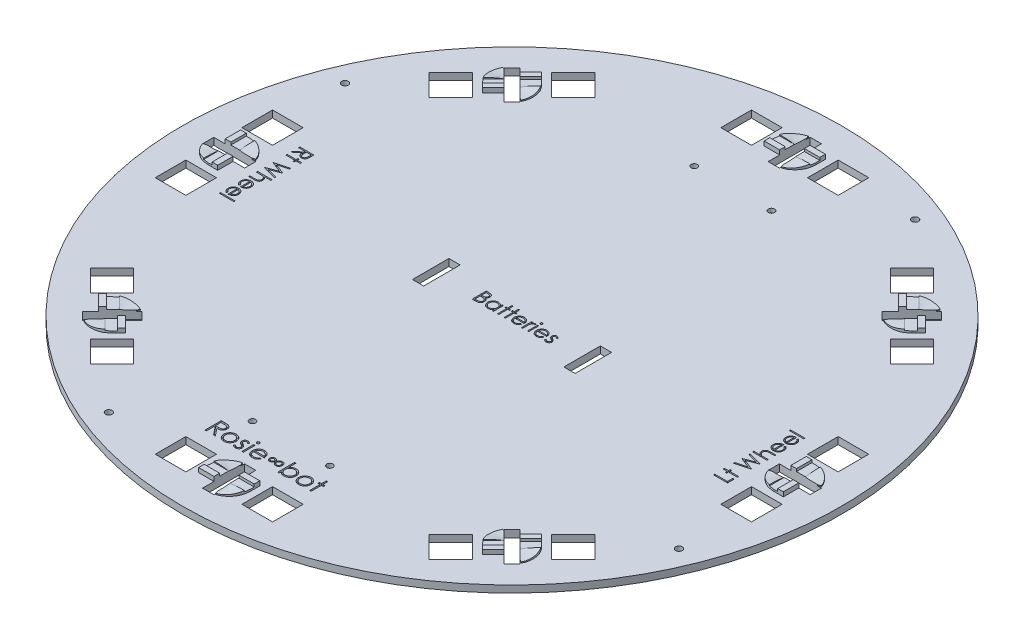
SolidWorks part; units mm, degrees
other "DetailItem1"
ref_plane "Front" through (0, 0, 0) normal (0, 0, 1) x (1, 0, 0)
ref_plane "Top" through (0, 0, 0) normal (0, 1, 0) x (1, 0, 0)
ref_plane "Right" through (0, 0, 0) normal (1, 0, 0) x (0, 0, -1)
sketch "Sketch1" plane through (0, 0, 0) normal (0, 1, 0) x (1, 0, 0)
  circle A0 centre (0, 0) radius 149.225
  dimension "D1" = 298.45
extrude "Boss-Extrude1" add sketch "Sketch1" along normal blind 3.175 contours A0
sketch "Sketch2" plane through (0, 3.175, 0) normal (0, 1, 0) x (1, 0, 0)
  line L1 (-2.54, -137.5833) -> (2.54, -137.5833)
  line L2 (-2.54, -137.5833) -> (-2.54, -118.5333)
  line L3 (-2.54, -118.5333) -> (2.54, -118.5333)
  line L4 (2.54, -137.5833) -> (2.54, -118.5333)
  circle A0 centre (0, 0) radius 149.225 construction
  point P4 (0, -118.5333)
  dimension "D1" = 5.08
  dimension "D2" = 19.05
  dimension "D3" = 137.5833
extrude "Cut-Extrude1" cut sketch "Sketch2" against normal up to next and the other way through all contours L1 L4 L3 L2
sketch "Sketch4" plane through (0, 3.175, 0) normal (0, 1, 0) x (1, 0, 0)
  line L0 (0, -128.0583) -> (-2.9434, -118.9995) construction
  line L1 (-2.9434, -118.9995) -> (0, -128.0583) construction
  line L2 (0, -128.0583) -> (-5.5987, -120.3525) construction
  line L3 (0, -128.0583) -> (-7.7059, -122.4597) construction
  line L4 (0, -128.0583) -> (-9.0588, -125.115) construction
  line L5 (0, -128.0583) -> (-9.525, -128.0583) construction
  line L9 (2.54, -118.5333) -> (-2.54, -118.5333) construction
  line L10 (2.54, -118.5333) -> (2.54, -137.5833) construction
  line L11 (-2.54, -118.5333) -> (-2.54, -137.5833) construction
  line L12 (2.54, -137.5833) -> (-2.54, -137.5833) construction
  circle A0 centre (0, -128.0583) radius 9.525 construction
  point P16 (0, -118.5333)
  point P19 (2.54, -128.0583)
  dimension "D1" = 18
  dimension "D2" = 18
  dimension "D3" = 18
  dimension "D4" = 18
  dimension "D5" = 18
ref_plane "Plane1" through (-37.6354, 0, 12.2285) normal (0.9511, 0, -0.309) x (-0.309, 0, -0.9511)
ref_plane "Plane2" through (-60.8954, 0, 44.2431) normal (0.809, 0, -0.5878) x (-0.5878, 0, -0.809)
ref_plane "Plane3" through (-60.8954, 0, 83.8153) normal (0.5878, 0, -0.809) x (-0.809, 0, -0.5878)
ref_plane "Plane4" through (-37.6354, 0, 115.8299) normal (0.309, 0, -0.9511) x (-0.9511, 0, -0.309)
ref_plane "Plane5" through (0, 0, 128.0583) normal (0, 0, -1) x (-1, 0, 0)
sketch "Sketch5" plane through (-37.6354, 0, 12.2285) normal (0.9511, 0, -0.309) x (-0.309, 0, -0.9511)
  line L0 (-111.947, 3.175) -> (-130.0646, 3.175) construction
  line L1 (-113.5711, 3.175) -> (-112.2657, 3.175)
  line L2 (-113.5711, 3.175) -> (-113.5711, 3.683)
  line L3 (-113.5711, 3.683) -> (-112.2657, 3.683)
  line L4 (-112.2657, 3.175) -> (-112.2657, 3.683)
  dimension "D2" = 0.508
sketch "Sketch6" plane through (-60.8954, 0, 44.2431) normal (0.809, 0, -0.5878) x (-0.5878, 0, -0.809)
  line L0 (-94.4025, 3.175) -> (-109.8143, 3.175) construction
  line L1 (-99.2801, 3.175) -> (-94.0764, 3.175)
  line L2 (-99.2801, 3.175) -> (-99.2801, 3.775)
  line L3 (-99.2801, 3.775) -> (-94.0764, 3.775)
  line L4 (-94.0764, 3.175) -> (-94.0764, 3.775)
  dimension "D2" = 0.6
sketch "Sketch7" plane through (-60.8954, 0, 83.8153) normal (0.5878, 0, -0.809) x (-0.809, 0, -0.5878)
  line L0 (-67.6172, 3.175) -> (-78.8146, 3.175) construction
  line L1 (-72.1312, 3.175) -> (-65.7458, 3.175)
  line L2 (-72.1312, 3.175) -> (-72.1312, 4.075)
  line L3 (-72.1312, 4.075) -> (-65.7458, 4.075)
  line L4 (-65.7458, 3.175) -> (-65.7458, 4.075)
  dimension "D2" = 0.9
sketch "Sketch10" plane through (-37.6354, 0, 115.8299) normal (0.309, 0, -0.9511) x (-0.9511, 0, -0.309)
  line L0 (-39.5722, 3.175) -> (-30.5134, 3.175) construction
  line L1 (-36.9015, 3.175) -> (-30.0472, 3.175)
  line L2 (-36.9015, 3.175) -> (-36.9015, 4.475)
  line L3 (-36.9015, 4.475) -> (-30.0472, 4.475)
  line L4 (-30.0472, 3.175) -> (-30.0472, 4.475)
  dimension "D3" = 1.3
sketch "Sketch11" plane through (0, 0, 128.0583) normal (0, 0, -1) x (-1, 0, 0)
  line L0 (0, 3.175) -> (9.525, 3.175) construction
  line L1 (2.54, 3.175) -> (9.525, 3.175)
  line L2 (2.54, 3.175) -> (2.54, 4.575)
  line L3 (2.54, 4.575) -> (9.525, 4.575)
  line L4 (9.525, 3.175) -> (9.525, 4.575)
  dimension "D3" = 1.4
loft "Loft1" add profiles "Sketch5", "Sketch6", "Sketch7", "Sketch10", "Sketch11" connector at (-2.54, 3.683, 120.241) connector at (-2.54, 3.775, 124.5623) connector at (-2.54, 4.075, 126.2129) connector at (-2.54, 4.475, 127.233) connector at (-2.54, 4.575, 128.0583)
sketch "Sketch13" plane through (-104.9799, 0, 128.0583) normal (0, 0, -1) x (-1, 0, 0)
  line L6 (-95.4549, 3.175) -> (-102.4399, 3.175)
  line L7 (-95.4549, 3.175) -> (-95.4549, 4.575)
  line L8 (-95.4549, 4.575) -> (-102.4399, 4.575)
  line L9 (-102.4399, 3.175) -> (-102.4399, 4.575)
extrude "Boss-Extrude4" add sketch "Sketch13" against normal blind 1.7907
sketch "Sketch25" plane through (0, 0, 129.849) normal (0, 0, 1) x (1, 0, 0)
  line L0 (-9.525, 4.575) -> (-2.54, 4.575) construction
  line L1 (-9.525, 3.175) -> (-2.54, 3.175)
  line L2 (-9.525, 3.175) -> (-9.525, 5.175)
  line L3 (-9.525, 5.175) -> (-2.54, 5.175)
  line L4 (-2.54, 3.175) -> (-2.54, 5.175)
  dimension "D1" = 0.6
extrude "Boss-Extrude5" add sketch "Sketch25" along normal blind 2.54
sketch "Sketch29" plane through (-2.54, 0, 0) normal (1, 0, 0) x (0, 0, -1)
  line L1 (-129.849, 5.175) -> (-125.749, 5.175)
  line L2 (-129.849, 5.175) -> (-129.849, 4)
  line L3 (-129.849, 4) -> (-125.749, 4)
  line L4 (-125.749, 5.175) -> (-125.749, 4)
  line L5 (-118.5333, 0) -> (-137.5833, 0) construction
  dimension "D1" = 4.1
  dimension "D2" = 4
extrude "Cut-Extrude10" cut sketch "Sketch29" against normal up to next
sketch "Sketch14" plane through (-2.54, 0, 0) normal (1, 0, 0) x (0, 0, -1)
  line L0 (-128.0583, 3.175) -> (-128.0583, 0) construction
  line L1 (-118.5333, 0) -> (-137.5833, 0) construction
ref_plane "Plane6" through (0, 0, 0) normal (1, 0, 0) x (0, 0, -1)
sketch "Sketch15" plane through (0, 0, 0) normal (1, 0, 0) x (0, 0, -1)
  line L0 (-128.0583, 0) -> (-128.0583, 3.175) construction
pattern_circular "CirPattern1" count 2 over 360 about axis through (0, 0, 128.0583) along (0, 1, 0) of "Loft1", "Boss-Extrude5", "Boss-Extrude4", "Cut-Extrude10" reverse direction yes
ref_axis "Axis1" through (0, 50, 0) along (0, -1, 0)
pattern_circular "CirPattern5" count 8 over 360 about axis through (0, 50, 0) along (0, -1, 0) of "CirPattern1", "Cut-Extrude1"
sketch "Sketch18" plane through (0, 3.175, 0) normal (0, 1, 0) x (1, 0, 0)
  line L4 (0, -149.225) -> (0, 149.225) construction
  line L5 (0, -1.7463) -> (0, 1.7463) construction
  line L6 (-149.225, 0) -> (149.225, 0) construction
  circle A8 centre (0, 0) radius 149.225 construction
sketch "Sketch19" plane through (0, 3.175, 0) normal (0, 1, 0) x (1, 0, 0)
  line L0 (-53.4609, -129.066) -> (0, 0) construction
  line L1 (0, -149.225) -> (0, 149.225) construction
  circle A1 centre (-53.4609, -129.066) radius 1.5
  dimension "D1" = 139.7
  dimension "D4" = 3
  dimension "D5" = 22.5
extrude "Cut-Extrude2" cut sketch "Sketch19" against normal through all
pattern_circular "CirPattern7" count 4 over 360 about axis through (0, 50, 0) along (0, -1, 0) of "Cut-Extrude2"
sketch "Sketch23" plane through (0, 3.175, 0) normal (0, 1, 0) x (1, 0, 0)
  line L9 (-2.54, -132.389) -> (-2.54, -137.5833) construction
  line L10 (-26.5557, -121.1305) -> (-12.7, -121.1305)
  line L11 (-26.5557, -121.1305) -> (-26.5557, -134.9862)
  line L16 (-26.5557, -134.9862) -> (-12.7, -134.9862)
  line L17 (-12.7, -121.1305) -> (-12.7, -134.9862)
  line L19 (2.54, -118.5333) -> (2.54, -123.7276) construction
  line L20 (0, -50) -> (0, 50) construction
  line L21 (12.7, -121.1305) -> (12.7, -134.9862)
  line L22 (26.5557, -134.9862) -> (12.7, -134.9862)
  line L23 (26.5557, -121.1305) -> (26.5557, -134.9862)
  line L24 (26.5557, -121.1305) -> (12.7, -121.1305)
  point P8 (-2.54, -134.9862)
  point P9 (2.54, -121.1305)
  dimension "D2" = 10.16
extrude "Cut-Extrude6" cut sketch "Sketch23" against normal through all
pattern_circular "CirPattern8" count 8 over 360 about axis through (0, 50, 0) along (0, -1, 0) of "Cut-Extrude6"
sketch "Sketch16" plane through (0, 3.175, 0) normal (0, 1, 0) x (1, 0, 0)
  line L1 (-16.4163, -2.4279) -> (16.4163, -2.4279) construction
  line L2 (0, -149.225) -> (0, 149.225) construction
  line L3 (-114.3, 19.05) -> (-114.3, -19.05) construction
  line L4 (-149.225, 0) -> (149.225, 0) construction
  line L5 (114.3, 19.05) -> (114.3, -19.05) construction
  line L6 (-25.719, -114.3) -> (25.719, -114.3) construction
  circle A2 centre (0, 0) radius 114.3 construction
  text T0 "Rosie∞bot\r\n" font "Century Gothic" height in points 28
  text T1 "Batteries"
  text T2 "Rt Wheel\r\n"
  text T3 "Lt Wheel"
  point P4 (-114.3, 0)
  point P7 (0, -114.3)
  point P10 (0, -2.4279)
  point P15 (114.3, 0)
  dimension "D7" = 228.6
  dimension "D1" = 32.8326
  dimension "D2" = 38.1
  dimension "D3" = 51.438
extrude "Cut-Extrude4" cut sketch "Sketch16" against normal blind 1.27
sketch "Sketch26" plane through (0, 3.175, 0) normal (0, 1, 0) x (1, 0, 0)
  line L0 (-149.225, 0) -> (149.225, 0) construction
  line L1 (-36.83, 8.255) -> (-31.75, 8.255)
  line L2 (-36.83, 8.255) -> (-36.83, -8.255)
  line L3 (-36.83, -8.255) -> (-31.75, -8.255)
  line L4 (-31.75, 8.255) -> (-31.75, -8.255)
  line L5 (0, -149.225) -> (0, 149.225) construction
  point P4 (-36.83, 0)
  dimension "D1" = 16.51
  dimension "D2" = 5.08
  dimension "D3" = 31.75
extrude "Cut-Extrude7" cut sketch "Sketch26" against normal through all
mirror "Mirror1" about plane through (0, 0, 0) normal (1, 0, 0) of "Cut-Extrude7"
sketch "Sketch27" plane through (0, 0, 0) normal (0, -1, 0) x (1, 0, 0)
  line L0 (0, 149.225) -> (0, -149.225) construction
  line L1 (-149.225, 0) -> (149.225, 0) construction
  circle A0 centre (-17.5, -100) radius 1.4
  dimension "D3" = 2.8
  dimension "D1" = 17.5
  dimension "D2" = 100
extrude "Cut-Extrude8" cut sketch "Sketch27" against normal through all both and the other way through all
mirror "Mirror2" about plane through (0, 0, 0) normal (1, 0, 0) of "Cut-Extrude8"
mirror "Mirror3" about plane through (0, 0, 0) normal (0, 0, 1) of "Mirror2"
sketch "Sketch28" plane through (0, 0, 0) normal (0, -1, 0) x (-1, 0, 0)
  line L0 (19.05, 101.6) -> (-19.05, 101.6) construction
  line L1 (0, -149.225) -> (0, 149.225) construction
  line L2 (149.225, 0) -> (-149.225, 0) construction
  line L3 (19.05, -101.6) -> (-19.05, -101.6) construction
  text T0 "Bk Caster"
  text T1 "Ft Caster"
  point P2 (0, 101.6)
  point P6 (0, -101.6)
  dimension "D1" = 101.6
  dimension "D2" = 38.1
  dimension "D3" = 101.6
extrude "Cut-Extrude9" cut sketch "Sketch28" against normal blind 1.27
